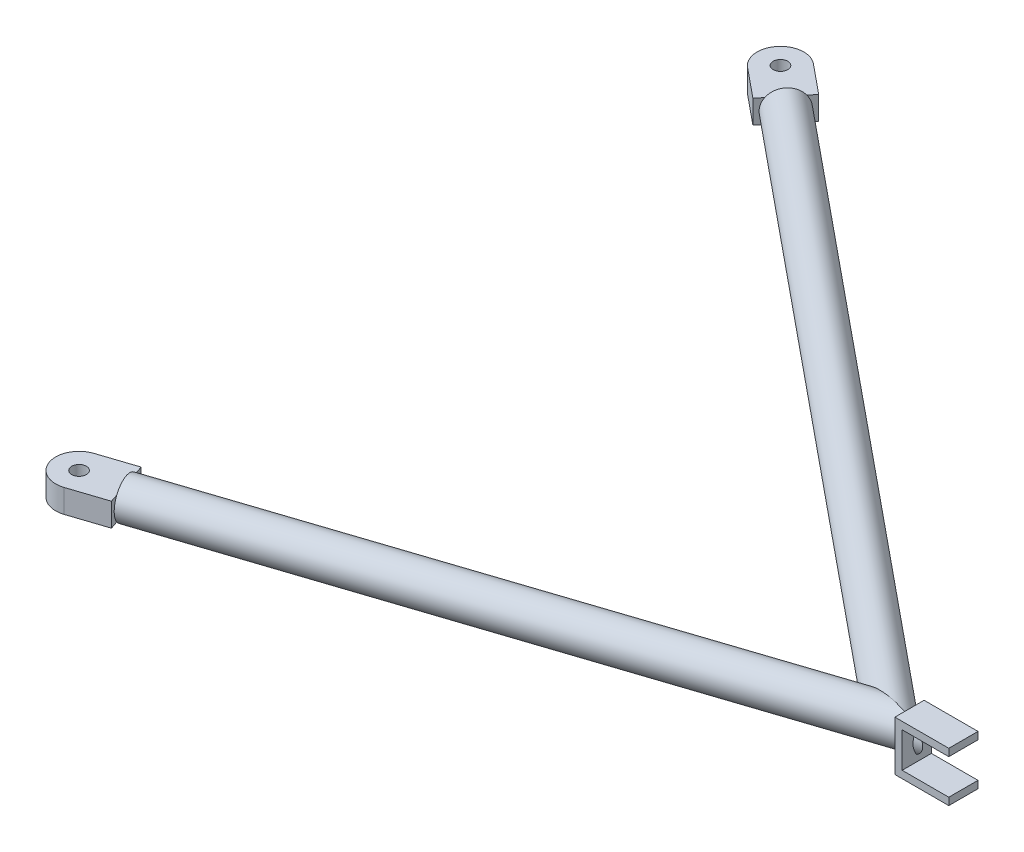
SolidWorks part; units mm, degrees
ref_plane "Front Plane" through (0, 0, 0) normal (0, 0, 1) x (1, 0, 0)
ref_plane "Top Plane" through (0, 0, 0) normal (0, 1, 0) x (1, 0, 0)
ref_plane "Right Plane" through (0, 0, 0) normal (1, 0, 0) x (0, 0, -1)
sketch "Sketch1" plane through (0, 0, 0) normal (0, 1, 0) x (1, 0, 0)
  line L0 (-265.3198, -87.5771) -> (0, 0)
  line L1 (0, 0) -> (-265.3198, 217.2229)
  line L2 (-265.3198, 217.2229) -> (-265.3198, -87.5771) construction
  dimension "D1" = 279.4
  dimension "D2" = 342.9
  dimension "D3" = 304.8
ref_plane "Plane1" through (-265.3198, 0, 87.5771) normal (0.9496, 0, -0.3134) x (-0.3134, 0, -0.9496)
sketch "Sketch2" plane through (-265.3198, 0, 87.5771) normal (0.9496, 0, -0.3134) x (-0.3134, 0, -0.9496)
  circle A0 centre (0, 0) radius 8.255
  dimension "D1" = 16.51
sweep "Sweep1" add profiles "Sketch2" path "Sketch1"
sketch "Sketch3" plane through (0, 0, 0) normal (0, 0, 1) x (1, 0, 0)
  line L0 (33.9318, 10.795) -> (10.504, 10.795)
  line L1 (10.504, 10.795) -> (10.504, -10.795)
  line L2 (10.504, -10.795) -> (33.9318, -10.795)
  line L3 (33.9318, -10.795) -> (33.9318, -7.62)
  line L4 (33.9318, -7.62) -> (13.679, -7.62)
  line L5 (13.679, -7.62) -> (13.679, 7.62)
  line L6 (13.679, 7.62) -> (33.9318, 7.62)
  line L7 (33.9318, 7.62) -> (33.9318, 10.795)
  line L8 (16.854, 0) -> (-16.854, 0) construction
  ellipse E0 centre (0, 0) end of major axis (16.854, 0) minor radius 8.255 construction
  ellipse E1 centre (0, 0) end of major axis (16.854, 0) minor radius 8.255 construction
  point P21 (10.504, 0)
  dimension "D1" = 3.175
  dimension "D2" = 15.24
  dimension "D3" = 3.175
  dimension "D4" = 6.35
extrude "Boss-Extrude1" add sketch "Sketch3" along normal blind 8.89 and the other way blind 3.81
sketch "Sketch4" plane through (-265.3198, 0, 87.5771) normal (-0.9496, 0, 0.3134) x (0.3134, 0, 0.9496)
  line L1 (-10.16, 5.08) -> (10.16, 5.08)
  line L2 (-10.16, 5.08) -> (-10.16, -5.08)
  line L3 (-10.16, -5.08) -> (10.16, -5.08)
  line L4 (10.16, 5.08) -> (10.16, -5.08)
  line L5 (-10.16, 5.08) -> (10.16, -5.08) construction
  line L6 (-10.16, -5.08) -> (10.16, 5.08) construction
  circle A1 centre (0, 0) radius 8.255
  circle A2 centre (0, 0) radius 8.255 construction
  dimension "D2" = 20.32
  dimension "D3" = 10.16
  dimension "D1" = 0
extrude "Boss-Extrude2" add sketch "Sketch4" along normal blind 10.16 and the other way blind 16.256
sketch "Sketch5" plane through (-265.3198, 0, -217.2229) normal (-0.7738, 0, -0.6335) x (-0.6335, 0, 0.7738)
  line L1 (-10.16, 5.08) -> (10.16, 5.08)
  line L2 (-10.16, 5.08) -> (-10.16, -5.08)
  line L3 (-10.16, -5.08) -> (10.16, -5.08)
  line L4 (10.16, 5.08) -> (10.16, -5.08)
  line L5 (-10.16, 5.08) -> (10.16, -5.08) construction
  line L6 (-10.16, -5.08) -> (10.16, 5.08) construction
  point P0 (0, 0)
  dimension "D1" = 20.32
  dimension "D2" = 10.16
extrude "Boss-Extrude3" add sketch "Sketch5" along normal blind 10.16 and the other way blind 16.51
sketch "Sketch6" plane through (0, 5.08, 0) normal (0, 1, 0) x (1, 0, 0)
  line L0 (-246.1089, 214.6254) -> (-266.7449, 231.5205) construction
  line L1 (-258.9814, 198.9027) -> (-279.6174, 215.7978) construction
  line L2 (-279.6174, 215.7978) -> (-266.7449, 231.5205) construction
  line L3 (-271.7561, 209.3616) -> (-279.6174, 215.7978)
  line L4 (-279.6174, 215.7978) -> (-273.1812, 223.6592)
  arc A0 (-273.1812, 223.6592) -> (-271.7561, 209.3616) centre (-265.3198, 217.2229) ccw
extrude "Cut-Extrude1" cut sketch "Sketch6" against normal through all
ref_plane "Plane2" through (0, 0, 0) normal (-0.6335, 0, 0.7738) x (0.7738, 0, 0.6335)
ref_plane "Plane3" through (0, 0, 0) normal (0.3134, 0, 0.9496) x (0.9496, 0, -0.3134)
mirror "Mirror1" about plane through (0, 0, 0) normal (-0.6335, 0, 0.7738) of "Cut-Extrude1"
sketch "Sketch7" plane through (0, 5.08, 0) normal (0, 1, 0) x (1, 0, 0)
  line L0 (-246.6984, -92.1297) -> (-271.7832, -100.4097) construction
  line L1 (-253.0677, -72.8337) -> (-278.1524, -81.1137) construction
  line L2 (-271.7832, -100.4097) -> (-278.1524, -81.1137) construction
  line L3 (-262.1352, -97.2251) -> (-271.7832, -100.4097)
  line L4 (-271.7832, -100.4097) -> (-274.9678, -90.7617)
  arc A0 (-262.1352, -97.2251) -> (-274.9678, -90.7617) centre (-265.3198, -87.5771) cw
extrude "Cut-Extrude2" cut sketch "Sketch7" against normal through all
mirror "Mirror2" about plane through (0, 0, 0) normal (0.3134, 0, 0.9496) of "Cut-Extrude2"
sketch "Sketch8" plane through (-265.3198, 0, 87.5771) normal (-0.9496, 0, 0.3134) x (0.3134, 0, 0.9496)
  line L0 (6.5068, -5.08) -> (-6.5068, -5.08) construction
  line L1 (-6.5068, 5.08) -> (6.5068, 5.08) construction
  line L2 (6.5068, -5.08) -> (-6.5068, -5.08)
  line L3 (-6.5068, 5.08) -> (6.5068, 5.08)
  arc A0 (-6.5068, -5.08) -> (6.5068, -5.08) centre (0, 0) ccw construction
  arc A1 (6.5068, 5.08) -> (-6.5068, 5.08) centre (0, 0) ccw construction
  arc A2 (-6.5068, -5.08) -> (6.5068, -5.08) centre (0, 0) ccw
  arc A3 (6.5068, 5.08) -> (-6.5068, 5.08) centre (0, 0) ccw
extrude "Cut-Extrude3" cut sketch "Sketch8" against normal up to surface (16.256 mm away) up to face at (-247.134, 0, 90.8102)
sketch "Sketch9" plane through (-265.3198, 0, -217.2229) normal (-0.7738, 0, -0.6335) x (-0.6335, 0, 0.7738)
  line L0 (6.5068, -5.08) -> (-6.5068, -5.08) construction
  line L1 (-6.5068, 5.08) -> (6.5068, 5.08) construction
  line L2 (6.5068, -5.08) -> (-6.5068, -5.08)
  line L3 (-6.5068, 5.08) -> (6.5068, 5.08)
  arc A0 (-6.5068, -5.08) -> (6.5068, -5.08) centre (0, 0) ccw construction
  arc A1 (6.5068, 5.08) -> (-6.5068, 5.08) centre (0, 0) ccw construction
  arc A2 (-6.5068, -5.08) -> (6.5068, -5.08) centre (0, 0) ccw
  arc A3 (6.5068, 5.08) -> (-6.5068, 5.08) centre (0, 0) ccw
extrude "Cut-Extrude4" cut sketch "Sketch9" against normal up to surface (16.51 mm away) up to face at (-258.1011, 0, -199.9779)
sketch "Sketch10" plane through (0, 5.08, 0) normal (0, 1, 0) x (1, 0, 0)
  point P0 (-265.3198, 217.2229)
  point P1 (-265.3198, -87.5771)
hole_wizard "E (0.25) Diameter Hole1" positions "3DSketch1" profile "Sketch11" hole size "E" standard "ANSI Inch"
sketch3d "3DSketch1"
  point P0 (-265.3198, 5.08, -217.2229)
  point P3 (-265.3198, 5.08, 87.5771)
sketch "Sketch11" plane through (-265.3198, 5.08, -217.2229) normal (1, 0, 0) x (0, 0, 1)
  line L0 (0, 0) -> (0, 20.9577)
  line L1 (0, 20.9577) -> (3.175, 19.05)
  line L2 (3.175, 19.05) -> (3.175, 0)
  line L5 (3.175, 0) -> (0, 0)
  line L10 (0, 20.9577) -> (-3.175, 19.05) construction
  line L11 (0, -6.35) -> (0, 107.95) construction
  dimension "Hole Dia." = 6.35
  dimension "Hole Depth" = 19.05
  dimension "Drill Angle" = 118
